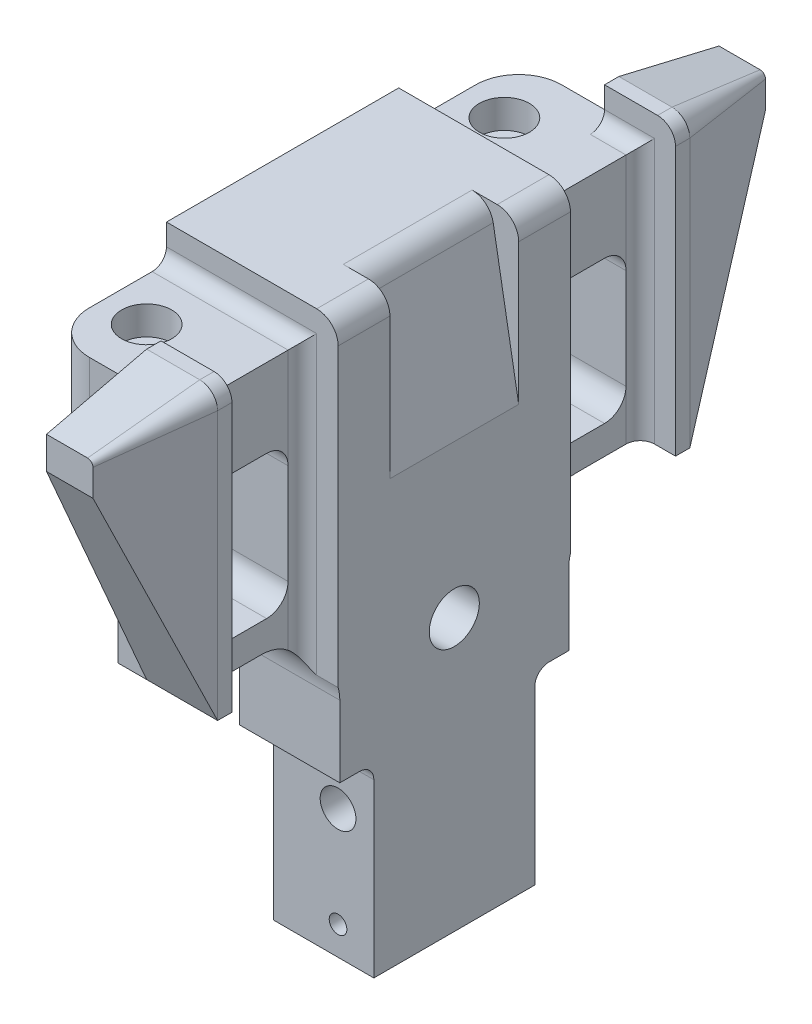
SolidWorks part; units mm, degrees
material "Nylatron"
ref_plane "Front Plane" through (0, 0, 0) normal (0, 0, 1) x (1, 0, 0)
ref_plane "Top Plane" through (0, 0, 0) normal (0, 1, 0) x (1, 0, 0)
ref_plane "Right Plane" through (0, 0, 0) normal (1, 0, 0) x (0, 0, -1)
sketch "Sketch1" plane through (0, 0, 0) normal (0, 0, 1) x (1, 0, 0)
  line L1 (-19.05, 65.0875) -> (19.05, 65.0875)
  line L2 (-19.05, 65.0875) -> (-19.05, -65.0875)
  line L3 (-19.05, -65.0875) -> (19.05, -65.0875)
  line L4 (19.05, 65.0875) -> (19.05, -65.0875)
  line L5 (-19.05, 65.0875) -> (19.05, -65.0875) construction
  line L6 (-19.05, -65.0875) -> (19.05, 65.0875) construction
  point P0 (0, 0)
  dimension "Width" = 38.1
  dimension "Height" = 130.175
extrude "Extrude1" add sketch "Sketch1" along normal mid plane 149.225
sketch "Sketch3" plane through (-19.05, 0, 0) normal (-1, 0, 0) x (0, 0, 1)
  line L0 (74.6125, 65.0875) -> (-74.6125, 65.0875) construction
  line L1 (-52.3875, 65.0875) -> (-74.6125, 59.836)
  line L2 (-74.6125, 59.836) -> (-74.6125, 65.0875)
  line L4 (-74.6125, 65.0875) -> (-52.3875, 65.0875)
  dimension "D1" = 5.2515
  dimension "D2" = 22.225
extrude "Cut-Extrude2" cut sketch "Sketch3" against normal through all
sketch "Sketch4" plane through (0, 65.0875, 0) normal (0, 1, 0) x (1, 0, 0)
  line L1 (13.4937, 74.6125) -> (18.923, 52.3875)
  line L3 (18.923, 52.3875) -> (18.923, 49.2125)
  line L5 (14.2875, 49.2125) -> (18.923, 49.2125)
  line L7 (11.1125, 28.9433) -> (11.1125, 46.0375)
  line L9 (14.2875, 25.7683) -> (19.05, 25.7683)
  line L10 (19.05, -74.6125) -> (19.05, 52.3875) construction
  line L11 (19.05, 74.6125) -> (13.4937, 74.6125)
  line L13 (19.05, 74.6125) -> (19.05, 25.7683)
  line L14 (19.05, 74.6125) -> (-19.05, 74.6125) construction
  arc A0 (11.1125, 28.9433) -> (14.2875, 25.7683) centre (14.2875, 28.9433) ccw
  arc A1 (11.1125, 46.0375) -> (14.2875, 49.2125) centre (14.2875, 46.0375) cw
  dimension "D1" = 3.175
  dimension "D2" = 7.9375
  dimension "D3" = 48.8442
  dimension "D4" = 23.4442
  dimension "D5" = 0.127
  dimension "D6" = 5.5562
  dimension "D7" = 22.225
extrude "Cut-Extrude3" cut sketch "Sketch4" against normal through all
ref_plane "Plane1" through (0, 0, -52.3875) normal (0, 0, 1) x (1, 0, 0)
sketch "Sketch9" plane through (0, 0, -52.3875) normal (0, 0, 1) x (1, 0, 0)
  line L0 (18.923, 65.0875) -> (-19.05, 65.0875) construction
  line L1 (18.923, -65.0875) -> (18.923, 65.0875) construction
  line L2 (18.923, 65.0875) -> (14.9542, 65.0875)
  line L3 (18.923, 61.1187) -> (18.923, 65.0875)
  arc A1 (18.923, 61.1187) -> (14.9542, 65.0875) centre (14.9542, 61.1187) ccw
  dimension "D1" = 7.9375
sketch "Sketch10" plane through (0, 0, -74.6125) normal (0, 0, -1) x (-1, 0, 0)
  line L0 (-13.4937, 59.836) -> (19.05, 59.836) construction
  line L1 (-13.4937, -65.0875) -> (-13.4937, 59.836) construction
  line L2 (-13.4937, 58.6422) -> (-13.4937, 59.836)
  line L3 (-13.4937, 59.836) -> (-12.2999, 59.836)
  arc A0 (-12.2999, 59.836) -> (-13.4937, 58.6422) centre (-12.2999, 58.6422) ccw
  dimension "D1" = 2.3876
loft "Cut-Loft1" cut profiles "Sketch10", "Sketch9" connector at (12.3, 59.8361, -74.6125) connector at (14.9543, 65.0875, -52.3875)
mirror "Mirror1" about plane through (0, 0, 0) normal (0, 0, 1) of "Cut-Loft1", "Cut-Extrude2", "Cut-Extrude3"
sketch "Sketch5" plane through (19.05, 0, 0) normal (1, 0, 0) x (0, 0, -1)
  line L0 (-25.7683, 65.0875) -> (25.7683, 65.0875) construction
  line L1 (74.6125, -65.0875) -> (25.4, -65.0875)
  line L2 (74.6125, -65.0875) -> (74.6125, 1.5875)
  line L3 (74.6125, 1.5875) -> (34.925, 1.5875)
  line L4 (25.4, -65.0875) -> (25.4, -7.9375)
  line L5 (-74.6125, -65.0875) -> (-25.4, -65.0875)
  line L6 (-74.6125, -65.0875) -> (-74.6125, 1.5875)
  line L7 (-74.6125, 1.5875) -> (-34.925, 1.5875)
  line L8 (-25.4, -65.0875) -> (-25.4, -7.9375)
  line L10 (-25.7683, -65.0875) -> (25.7683, -65.0875) construction
  line L11 (-25.4, -7.9375) -> (25.4, -7.9375) construction
  line L12 (0, 0) -> (0, -7.9375) construction
  arc A0 (34.925, 1.5875) -> (25.4, -7.9375) centre (34.925, -7.9375) ccw
  arc A1 (-34.925, 1.5875) -> (-25.4, -7.9375) centre (-34.925, -7.9375) cw
  dimension "D3" = 9.525
  dimension "D1" = 50.8
  dimension "D2" = 63.5
extrude "Cut-Extrude4" cut sketch "Sketch5" against normal through all
sketch "Sketch8" plane through (0, 0, 0) normal (0, 0, 1) x (1, 0, 0)
  line L0 (19.05, 65.0875) -> (12.7, 65.0875)
  line L1 (14.9542, 65.0875) -> (-19.05, 65.0875) construction
  line L2 (12.7, 65.0875) -> (19.05, 29.0749)
  line L3 (19.05, -65.0875) -> (19.05, -7.9375) construction
  line L4 (19.05, 29.0749) -> (19.05, 65.0875)
  dimension "D1" = 10
  dimension "D2" = 6.35
extrude "Cut-Extrude7" cut sketch "Sketch8" against normal mid plane 28.575
fillet "Fillet1" radius 4.7625 1 edges at (12.7, 65.0875, 0)
fillet "Fillet2" radius 4.7625 2 edges at (19.05, 65.0875, -20.0279) (19.05, 65.0875, 20.0279)
fillet "Fillet5" radius 3.9688 1 edges at (18.923, 65.0875, -50.8) tangent propagation no
sketch "Sketch11" plane through (19.05, 0, 0) normal (1, 0, 0) x (0, 0, -1)
  line L1 (25.4, -65.0875) -> (17.8562, -65.0875)
  line L2 (25.4, -65.0875) -> (25.4, -23.8125)
  line L3 (25.4, -23.8125) -> (21.0312, -23.8125)
  line L4 (17.8562, -65.0875) -> (17.8562, -26.9875)
  line L5 (-25.4, -65.0875) -> (-17.8562, -65.0875)
  line L6 (-25.4, -65.0875) -> (-25.4, -23.8125)
  line L7 (-25.4, -23.8125) -> (-21.0312, -23.8125)
  line L8 (-17.8562, -65.0875) -> (-17.8562, -26.9875)
  arc A0 (21.0312, -23.8125) -> (17.8562, -26.9875) centre (21.0312, -26.9875) ccw
  arc A1 (-21.0312, -23.8125) -> (-17.8562, -26.9875) centre (-21.0312, -26.9875) cw
  dimension "D3" = 3.175
  dimension "D1" = 7.5438
  dimension "D2" = 41.275
extrude "Cut-Extrude8" cut sketch "Sketch11" against normal through all
hole_wizard "5/16 (0.3125) Diameter Hole1" positions "Sketch15" profile "Sketch16" hole size "5/16" standard "ANSI Inch"
sketch "Sketch15" plane through (0, 0, -17.8562) normal (0, 0, -1) x (-1, 0, 0)
  line L0 (19.05, -65.0875) -> (-19.05, -65.0875) construction
  line L1 (-19.05, -26.9875) -> (-19.05, -65.0875) construction
  point P0 (-11.1125, -36.5125)
  dimension "D1" = 28.575
  dimension "D2" = 7.9375
sketch "Sketch16" plane through (11.1125, -36.5125, -17.8562) normal (1, 0, 0) x (0, 1, 0)
  line L0 (0, 0) -> (0, 14.0687)
  line L1 (0, 14.0687) -> (3.9687, 11.684)
  line L2 (3.9687, 11.684) -> (3.9687, 0)
  line L5 (3.9687, 0) -> (0, 0)
  line L10 (0, 14.0687) -> (-3.9688, 11.684) construction
  line L11 (0, -6.35) -> (0, 107.95) construction
  dimension "Hole Dia." = 7.9375
  dimension "Hole Depth" = 11.684
  dimension "Drill Angle" = 118
hole_wizard "#23 (0.154) Diameter Hole1" positions "Sketch17" profile "Sketch18" hole size "#23" standard "ANSI Inch"
sketch "Sketch17" plane through (0, 0, -17.8562) normal (0, 0, -1) x (-1, 0, 0)
  line L0 (19.05, -65.0875) -> (-19.05, -65.0875) construction
  line L1 (-19.05, -26.9875) -> (-19.05, -65.0875) construction
  point P0 (-11.1125, -58.7375)
  dimension "D1" = 6.35
  dimension "D2" = 7.9375
sketch "Sketch18" plane through (11.1125, -58.7375, -17.8562) normal (1, 0, 0) x (0, 1, 0)
  line L0 (0, 0) -> (0, 12.8592)
  line L1 (0, 12.8592) -> (1.9558, 11.684)
  line L2 (1.9558, 11.684) -> (1.9558, 0)
  line L5 (1.9558, 0) -> (0, 0)
  line L10 (0, 12.8592) -> (-1.9558, 11.684) construction
  line L11 (0, -6.35) -> (0, 107.95) construction
  dimension "Hole Dia." = 3.9116
  dimension "Hole Depth" = 11.684
  dimension "Drill Angle" = 118
hole_wizard "#23 (0.154) Diameter Hole2" positions "Sketch19" profile "Sketch20" hole size "#23" standard "ANSI Inch"
sketch "Sketch19" plane through (0, 0, 17.8562) normal (0, 0, 1) x (1, 0, 0)
  point P0 (11.1125, -58.7375)
sketch "Sketch20" plane through (11.1125, -58.7375, 17.8562) normal (1, 0, 0) x (0, -1, 0)
  line L0 (0, 0) -> (0, 12.8592)
  line L1 (0, 12.8592) -> (1.9558, 11.684)
  line L2 (1.9558, 11.684) -> (1.9558, 0)
  line L5 (1.9558, 0) -> (0, 0)
  line L10 (0, 12.8592) -> (-1.9558, 11.684) construction
  line L11 (0, -6.35) -> (0, 107.95) construction
  dimension "Hole Dia." = 3.9116
  dimension "Hole Depth" = 11.684
  dimension "Drill Angle" = 118
hole_wizard "5/16 (0.3125) Diameter Hole2" positions "Sketch21" profile "Sketch22" hole size "5/16" standard "ANSI Inch"
sketch "Sketch21" plane through (0, 0, 17.8562) normal (0, 0, 1) x (1, 0, 0)
  point P0 (11.1125, -36.5125)
sketch "Sketch22" plane through (11.1125, -36.5125, 17.8562) normal (1, 0, 0) x (0, -1, 0)
  line L0 (0, 0) -> (0, 14.0687)
  line L1 (0, 14.0687) -> (3.9687, 11.684)
  line L2 (3.9687, 11.684) -> (3.9687, 0)
  line L5 (3.9687, 0) -> (0, 0)
  line L10 (0, 14.0687) -> (-3.9688, 11.684) construction
  line L11 (0, -6.35) -> (0, 107.95) construction
  dimension "Hole Dia." = 7.9375
  dimension "Hole Depth" = 11.684
  dimension "Drill Angle" = 118
sketch "Sketch23" plane through (18.923, 0, 0) normal (1, 0, 0) x (0, 0, -1)
  line L0 (25.7683, -5.3144) -> (25.7683, 65.0875) construction
  line L1 (28.9433, 57.15) -> (46.0375, 57.15)
  line L2 (25.7683, 60.325) -> (25.7683, 65.0875)
  line L3 (25.7683, 65.0875) -> (49.2125, 65.0875)
  line L4 (49.2125, 60.325) -> (49.2125, 65.0875)
  line L5 (14.2875, 65.0875) -> (25.7683, 65.0875) construction
  line L6 (49.2125, 65.0875) -> (52.3875, 65.0875) construction
  line L7 (49.2125, 1.5875) -> (49.2125, 61.1187) construction
  line L8 (-25.7683, -5.3144) -> (-25.7683, 60.325) construction
  line L9 (-49.2125, 65.0875) -> (-25.7683, 65.0875)
  line L10 (-49.2125, 65.0875) -> (-49.2125, 60.325)
  line L11 (-46.0375, 57.15) -> (-28.9433, 57.15)
  line L12 (-25.7683, 65.0875) -> (-25.7683, 60.325)
  arc A0 (46.0375, 57.15) -> (49.2125, 60.325) centre (46.0375, 60.325) ccw
  arc A1 (28.9433, 57.15) -> (25.7683, 60.325) centre (28.9433, 60.325) cw
  arc A2 (-28.9433, 57.15) -> (-25.7683, 60.325) centre (-28.9433, 60.325) ccw
  arc A3 (-49.2125, 60.325) -> (-46.0375, 57.15) centre (-46.0375, 60.325) ccw
  point P9 (49.2125, 57.15)
  point P12 (25.7683, 57.15)
  point P27 (-25.7683, 57.15)
  dimension "D2" = 3.175
  dimension "D3" = 3.175
  dimension "D1" = 7.9375
extrude "Cut-Extrude10" cut sketch "Sketch23" against normal through all
fillet "Fillet8" radius 3.9688 1 edges at (18.923, 65.0875, 50.8)
sketch "Sketch24" plane through (0, 0, 74.6125) normal (0, 0, 1) x (1, 0, 0)
  line L0 (-19.05, 59.836) -> (-19.05, 1.5875) construction
  line L1 (-19.05, 39.6875) -> (0, 39.6875)
  line L2 (-19.05, 39.6875) -> (-19.05, -65.0875)
  line L3 (-19.05, -65.0875) -> (3.175, -65.0875)
  line L4 (3.175, 36.5125) -> (3.175, -65.0875)
  line L5 (-19.05, -65.0875) -> (19.05, -65.0875) construction
  line L6 (14.9542, 65.0875) -> (-19.05, 65.0875) construction
  line L7 (19.05, -5.3144) -> (19.05, 60.325) construction
  arc A0 (0, 39.6875) -> (3.175, 36.5125) centre (0, 36.5125) cw
  dimension "D3" = 3.175
  dimension "D1" = 25.4
  dimension "D2" = 15.875
extrude "Cut-Extrude11" cut sketch "Sketch24" against normal through all
sketch "Sketch26" plane through (0, 65.0875, 0) normal (0, 1, 0) x (1, 0, 0)
  line L1 (-19.05, -74.6125) -> (3.175, -74.6125)
  line L2 (-19.05, -74.6125) -> (-19.05, -52.3875)
  line L3 (-19.05, -52.3875) -> (3.175, -52.3875)
  line L4 (3.175, -74.6125) -> (3.175, -52.3875)
  line L5 (-19.05, 74.6125) -> (3.175, 74.6125)
  line L6 (-19.05, 74.6125) -> (-19.05, 52.3875)
  line L7 (-19.05, 52.3875) -> (3.175, 52.3875)
  line L8 (3.175, 74.6125) -> (3.175, 52.3875)
  point P7 (3.175, -52.3875)
  dimension "D3" = 22.225
  dimension "D1" = 22.225
  dimension "D2" = 22.225
extrude "Cut-Extrude13" cut sketch "Sketch26" against normal through all
sketch "Sketch27" plane through (-19.05, 0, 0) normal (-1, 0, 0) x (0, 0, 1)
  line L1 (46.0375, 57.15) -> (52.3875, 57.15)
  line L2 (46.0375, 57.15) -> (46.0375, 65.0875)
  line L3 (46.0375, 65.0875) -> (52.3875, 65.0875)
  line L4 (52.3875, 57.15) -> (52.3875, 65.0875)
  line L6 (-52.3875, 65.0875) -> (-46.0375, 65.0875)
  line L7 (-52.3875, 65.0875) -> (-52.3875, 57.15)
  line L8 (-52.3875, 57.15) -> (-46.0375, 57.15)
  line L9 (-46.0375, 65.0875) -> (-46.0375, 57.15)
extrude "Cut-Extrude14" cut sketch "Sketch27" against normal up to surface (22.225 mm away) up to face at (3.175, 1.9604, 0)
hole_wizard "CBORE for 1/4 Socket Head Cap Screw2" positions "Sketch32" profile "Sketch33" counterbore size "1/4" standard "ANSI Inch" end condition up to next
sketch "Sketch32" plane through (19.05, 0, 0) normal (1, 0, 0) x (0, 0, -1)
  line L1 (14.2875, 65.0875) -> (25.7683, 65.0875) construction
  point P0 (0, -4.7625)
  dimension "D1" = 69.85
sketch "Sketch33" plane through (19.05, -4.7625, 0) normal (0, 1, 0) x (0, 0, -1)
  line L0 (0, 0) -> (0, 15.875)
  line L1 (0, 15.875) -> (3.3782, 15.875)
  line L3 (3.3782, 15.875) -> (3.3782, 9.525)
  line L4 (3.3782, 9.525) -> (5.5562, 9.525)
  line L5 (5.5562, 9.525) -> (5.5563, 0)
  line L7 (5.5563, 0) -> (0, 0)
  line L11 (0, -6.35) -> (0, 107.95) construction
  dimension "Thru Hole Dia." = 6.7564
  dimension "Thru Hole Depth" = 15.875
  dimension "C'Bore Dia." = 11.1125
  dimension "C'Bore Depth" = 9.525
sketch "Sketch34" plane through (3.175, 0, 0) normal (-1, 0, 0) x (0, 0, 1)
  line L0 (-52.3875, 39.6875) -> (52.3875, 39.6875) construction
  line L1 (52.3875, 33.0835) -> (52.3875, 1.5875)
  line L3 (-52.3875, 33.0835) -> (-52.3875, 1.5875)
  line L4 (-52.3875, 39.6875) -> (-52.3875, 57.15) construction
  line L5 (52.3875, 36.5125) -> (52.3875, 57.15) construction
  line L17 (34.925, 1.5875) -> (74.6125, 1.5875)
  line L18 (74.6125, 1.5875) -> (74.6125, 59.836)
  line L19 (74.6125, 59.836) -> (52.3875, 65.0875)
  line L20 (52.3875, 65.0875) -> (49.2125, 65.0875)
  line L21 (49.2125, 65.0875) -> (49.2125, 60.325)
  line L22 (46.0375, 57.15) -> (52.3875, 57.15)
  line L23 (52.3875, 57.15) -> (52.3875, 36.5125)
  line L24 (52.3875, 36.5125) -> (-52.3875, 36.5125)
  line L25 (-74.6125, 59.836) -> (-74.6125, 1.5875)
  line L26 (-74.6125, 1.5875) -> (-34.925, 1.5875)
  line L27 (-25.4, -7.9375) -> (-25.4, -23.8125)
  line L28 (-25.4, -23.8125) -> (-21.0312, -23.8125)
  line L29 (-17.8562, -26.9875) -> (-17.8562, -65.0875)
  line L30 (-17.8562, -65.0875) -> (17.8562, -65.0875)
  line L31 (17.8562, -65.0875) -> (17.8562, -26.9875)
  line L32 (21.0312, -23.8125) -> (25.4, -23.8125)
  line L33 (25.4, -23.8125) -> (25.4, -7.9375)
  line L34 (34.925, 1.5875) -> (52.3875, 1.5875)
  line L41 (52.3875, 33.0835) -> (-52.3875, 33.0835)
  line L43 (-52.3875, 1.5875) -> (-34.925, 1.5875)
  line L44 (-25.4, -7.9375) -> (-25.4, -23.8125)
  line L45 (-25.4, -23.8125) -> (-21.0312, -23.8125)
  line L46 (-17.8562, -26.9875) -> (-17.8562, -65.0875)
  line L47 (-17.8562, -65.0875) -> (17.8562, -65.0875)
  line L48 (17.8562, -65.0875) -> (17.8562, -26.9875)
  line L49 (21.0312, -23.8125) -> (25.4, -23.8125)
  line L50 (25.4, -23.8125) -> (25.4, -7.9375)
  line L56 (-52.3875, 36.5125) -> (-52.3875, 57.15)
  line L58 (-52.3875, 65.0875) -> (-74.6125, 59.836)
  line L63 (-52.3875, 57.15) -> (-46.0375, 57.15)
  line L65 (-49.2125, 60.325) -> (-49.2125, 65.0875)
  line L67 (-49.2125, 65.0875) -> (-52.3875, 65.0875)
  circle A0 centre (0, -4.7625) radius 3.3782 construction
  circle A1 centre (0, -4.7625) radius 3.3782
  arc A6 (34.925, 1.5875) -> (25.4, -7.9375) centre (34.925, -7.9375) ccw
  arc A7 (46.0375, 57.15) -> (49.2125, 60.325) centre (46.0375, 60.325) ccw
  arc A9 (-25.4, -7.9375) -> (-34.925, 1.5875) centre (-34.925, -7.9375) ccw
  arc A10 (-17.8562, -26.9875) -> (-21.0312, -23.8125) centre (-21.0312, -26.9875) ccw
  arc A11 (21.0312, -23.8125) -> (17.8562, -26.9875) centre (21.0312, -26.9875) ccw
  arc A12 (34.925, 1.5875) -> (25.4, -7.9375) centre (34.925, -7.9375) ccw
  arc A15 (-25.4, -7.9375) -> (-34.925, 1.5875) centre (-34.925, -7.9375) ccw
  arc A16 (-17.8562, -26.9875) -> (-21.0312, -23.8125) centre (-21.0312, -26.9875) ccw
  arc A17 (21.0312, -23.8125) -> (17.8562, -26.9875) centre (21.0312, -26.9875) ccw
  arc A19 (-49.2125, 60.325) -> (-46.0375, 57.15) centre (-46.0375, 60.325) ccw
  dimension "D2" = 6.604
  dimension "D1" = 0
extrude "Boss-Extrude1" add sketch "Sketch34" along normal blind 6.35
hole_wizard "#8-32 Tapped Hole1" positions "Sketch30" profile "Sketch31" tap size "#8-32" standard "ANSI Inch" end condition up to next
sketch "Sketch30" plane through (-3.175, 0, 0) normal (-1, 0, 0) x (0, 0, 1)
  line L0 (-17.8562, -65.0875) -> (17.8562, -65.0875) construction
  line L1 (17.8562, -26.9875) -> (17.8562, -65.0875) construction
  line L2 (-17.8562, -65.0875) -> (-17.8562, -26.9875) construction
  point P0 (-11.5062, -36.5125)
  point P2 (-11.5062, -58.7375)
  point P4 (11.5062, -36.5125)
  point P6 (11.5062, -58.7375)
  dimension "D1" = 6.35
  dimension "D2" = 28.575
  dimension "D3" = 6.35
  dimension "D4" = 6.35
sketch "Sketch31" plane through (-3.175, -36.5125, -11.5062) normal (0, 1, 0) x (0, 0, 1)
  line L0 (0, 0) -> (0, 10.3187)
  line L1 (0, 10.3187) -> (1.7272, 10.3187)
  line L2 (1.7272, 10.3187) -> (1.7272, 0)
  line L5 (1.7272, 0) -> (0, 0)
  line L11 (0, -6.35) -> (0, 107.95) construction
  dimension "Thru Tap Drill Dia." = 3.4544
  dimension "Thru Tap Drill Depth" = 10.3187
cosmetic thread "Hole Thread5" parameters "D2"=4.1656
cosmetic thread "Hole Thread6" parameters "D2"=4.1656
cosmetic thread "Hole Thread7" parameters "D2"=4.1656
cosmetic thread "Hole Thread8" parameters "D2"=4.1656
fillet "Fillet12" radius 3.175 1 edges at (3.175, 33.0835, 0)
fillet "Fillet13" radius 9.525 2 edges at (-19.05, 48.4187, 52.3875) (-19.05, 48.4187, -52.3875)
sketch "Sketch35" plane through (11.1125, 0, 0) normal (1, 0, 0) x (0, 0, -1)
  line L0 (-46.0375, 1.5875) -> (-46.0375, 57.15) construction
  line L3 (-41.275, 39.6875) -> (-33.7058, 39.6875)
  line L7 (-46.0375, 34.925) -> (-46.0375, 12.7)
  line L8 (-41.275, 7.9375) -> (-33.7058, 7.9375)
  line L9 (-28.9433, 34.925) -> (-28.9433, 12.7)
  line L10 (-28.9433, -0.525) -> (-28.9433, 57.15) construction
  line L11 (-52.3875, 1.5875) -> (-74.6125, 1.5875) construction
  line L12 (28.9433, -0.525) -> (28.9433, 57.15) construction
  line L13 (33.7058, 39.6875) -> (41.275, 39.6875)
  line L14 (28.9433, 34.925) -> (28.9433, 12.7)
  line L15 (33.7058, 7.9375) -> (41.275, 7.9375)
  line L16 (46.0375, 34.925) -> (46.0375, 12.7)
  line L17 (46.0375, 1.5875) -> (46.0375, 57.15) construction
  arc A2 (-46.0375, 12.7) -> (-41.275, 7.9375) centre (-41.275, 12.7) ccw
  arc A3 (-33.7058, 7.9375) -> (-28.9433, 12.7) centre (-33.7058, 12.7) ccw
  arc A4 (-33.7058, 39.6875) -> (-28.9433, 34.925) centre (-33.7058, 34.925) cw
  arc A5 (-41.275, 39.6875) -> (-46.0375, 34.925) centre (-41.275, 34.925) ccw
  arc A6 (28.9433, 12.7) -> (33.7058, 7.9375) centre (33.7058, 12.7) ccw
  arc A7 (41.275, 7.9375) -> (46.0375, 12.7) centre (41.275, 12.7) ccw
  arc A8 (41.275, 39.6875) -> (46.0375, 34.925) centre (41.275, 34.925) cw
  arc A9 (33.7058, 39.6875) -> (28.9433, 34.925) centre (33.7058, 34.925) ccw
  point P14 (-28.9433, 7.9375)
  point P19 (-46.0375, 39.6875)
  point P32 (46.0375, 7.9375)
  point P37 (28.9433, 39.6875)
  dimension "D3" = 4.7625
  dimension "D4" = 4.7625
  dimension "D1" = 6.35
  dimension "D2" = 38.1
extrude "Cut-Extrude15" cut sketch "Sketch35" against normal through all
sketch "Sketch38" plane through (18.923, 0, 0) normal (1, 0, 0) x (0, 0, -1)
  line L0 (-74.6125, 52.6923) -> (-52.3875, 1.5875)
  line L1 (-74.6125, 1.5875) -> (-74.6125, 58.6422) construction
  line L2 (-52.3875, 1.5875) -> (-74.6125, 1.5875)
  line L3 (-74.6125, 1.5875) -> (-74.6125, 52.6923)
  line L4 (52.3875, 1.5875) -> (74.6125, 52.6923)
  line L5 (74.6125, 1.5875) -> (74.6125, 58.6422) construction
  line L6 (74.6125, 52.6923) -> (74.6125, 1.5875)
  line L7 (74.6125, 1.5875) -> (52.3875, 1.5875)
  dimension "D1" = 7.1437
extrude "Cut-Extrude17" cut sketch "Sketch38" against normal through all
hole_wizard "CBORE for 1/4 Socket Head Cap Screw3" positions "Sketch39" profile "Sketch40" counterbore size "1/4" standard "ANSI Inch" end condition through all
sketch "Sketch39" plane through (0, 57.15, 0) normal (0, 1, 0) x (1, 0, 0)
  line L0 (-19.05, 28.9433) -> (-19.05, 42.8625) construction
  line L1 (3.175, 52.3875) -> (-9.525, 52.3875) construction
  line L2 (3.175, -52.3875) -> (-9.525, -52.3875) construction
  point P0 (-9.525, 39.6875)
  point P2 (-9.525, -39.6875)
  dimension "D1" = 9.525
  dimension "D2" = 12.7
  dimension "D3" = 12.7
sketch "Sketch40" plane through (-9.525, 57.15, -39.6875) normal (1, 0, 0) x (0, 0, 1)
  line L0 (0, 0) -> (0, 122.2375)
  line L1 (0, 122.2375) -> (3.3782, 122.2375)
  line L3 (3.3782, 122.2375) -> (3.3782, 6.35)
  line L4 (3.3782, 6.35) -> (5.5562, 6.35)
  line L5 (5.5562, 6.35) -> (5.5563, 0)
  line L7 (5.5563, 0) -> (0, 0)
  line L11 (0, -6.35) -> (0, 107.95) construction
  dimension "Thru Hole Dia." = 6.7564
  dimension "Thru Hole Depth" = 122.2375
  dimension "C'Bore Dia." = 11.1125
  dimension "C'Bore Depth" = 6.35
